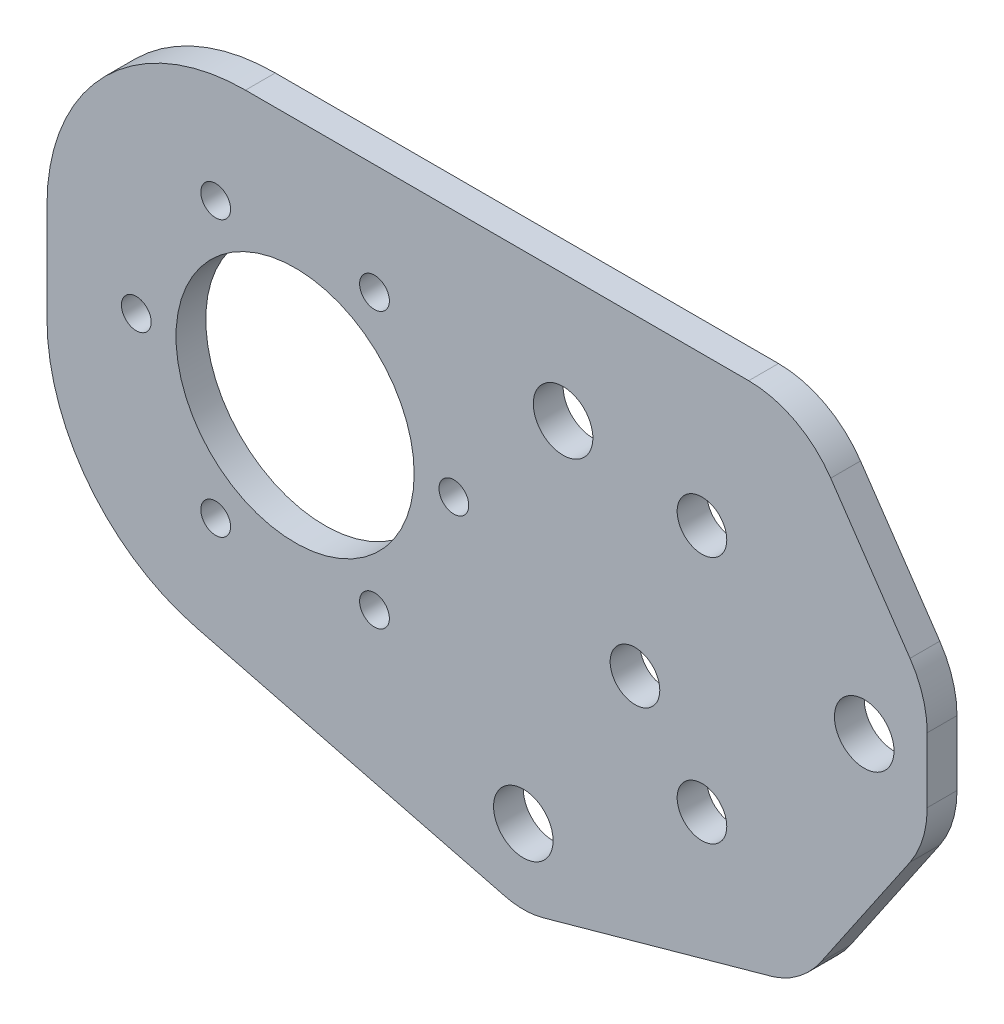
SolidWorks part; units mm, degrees
material "Gerais  - 6061-T6"
ref_plane "Plano frontal" through (0, 0, 0) normal (0, 0, 1) x (1, 0, 0)
ref_plane "Plano superior" through (0, 0, 0) normal (0, 1, 0) x (1, 0, 0)
ref_plane "Plano direito" through (0, 0, 0) normal (1, 0, 0) x (0, 0, -1)
sketch "Esboço1" plane through (0, 0, 0) normal (0, 0, 1) x (1, 0, 0)
  line L0 (56, 50) -> (56, 0) construction
  line L1 (0, 0) -> (76, 0)
  line L2 (0, 0) -> (0, 50)
  line L3 (0, 50) -> (76, 50)
  line L4 (76, 0) -> (76, 50)
  line L5 (66, 50) -> (66, 18.5) construction
  line L6 (65.25, 50) -> (65.25, 18.5) construction
  line L7 (59.25, 12.5) -> (25, 12.5) construction
  circle A0 centre (25, 25) radius 16 construction
  circle A1 centre (59.25, 18.5) radius 9.75 construction
  circle A2 centre (59.25, 18.5) radius 6 construction
  circle A3 centre (25, 25) radius 12.5 construction
  circle A4 centre (59.25, 18.5) radius 2.5
  circle A5 centre (25, 25) radius 12
  circle A6 centre (17, 38.8564) radius 1.5
  circle A7 centre (33, 38.8564) radius 1.5
  circle A8 centre (41, 25) radius 1.5
  circle A9 centre (33, 11.1436) radius 1.5
  circle A10 centre (17, 11.1436) radius 1.5
  circle A11 centre (9, 25) radius 1.5
  point P7 (41, 25)
  point P36 (25, 25)
  dimension "D1" = 32
  dimension "D5" = 12
  dimension "D6" = 19.5
  dimension "D9" = 25
  dimension "D10" = 5
  dimension "D13" = 24
  dimension "D14" = 3
  dimension "D2" = 25
  dimension "D3" = 35
  dimension "D4" = 20
  dimension "D7" = 0.75
  dimension "D8" = 10
  dimension "D11" = 25
  dimension "D12" = 50
  dimension "D15" = 6
extrude "Ressalto-extrusão1" add sketch "Esboço1" along normal blind 3
sketch "Esboço2" plane through (0, 0, 3) normal (0, 0, 1) x (1, 0, 0)
  line L0 (66, 50) -> (66, 0) construction
  line L1 (76, 50) -> (0, 50) construction
  line L2 (0, 0) -> (76, 0) construction
  line L3 (76, 0) -> (76, 50) construction
  circle A0 centre (66, 35) radius 2.5
  circle A1 centre (66, 15) radius 2.5
  dimension "D2" = 5
  dimension "D3" = 5
  dimension "D1" = 10
  dimension "D4" = 15
  dimension "D5" = 15
extrude "Corte-extrusão1" cut sketch "Esboço2" against normal blind 3
fillet "Filete1" radius 20 2 edges at (0, 0, 1.5) (0, 50, 1.5)
sketch "Esboço3" plane through (0, 0, 3) normal (0, 0, 1) x (1, 0, 0)
  circle A0 centre (66, 15) radius 2.5 construction
  circle A1 centre (66, 35) radius 2.5 construction
  circle A2 centre (66, 15) radius 2.5
  circle A3 centre (66, 35) radius 2.5
extrude "Ressalto-extrusão2" add sketch "Esboço3" against normal through all
sketch "Esboço4" plane through (0, 0, 0) normal (0, 0, -1) x (-1, 0, 0)
  line L0 (-20, 0) -> (-76, 0) construction
  line L1 (-20, 0) -> (-76, 0)
  line L5 (-78.9768, 45.6286) -> (-86.9656, 33.897)
  line L6 (-73.1059, -0.8046) -> (-50.0089, -7.2259)
  line L7 (-46.1556, -7.2697) -> (-15.0816, 0.6142)
  line L8 (0, 20) -> (0, 30)
  line L9 (-20, 50) -> (-70.7112, 50)
  line L11 (-73.1059, -0.8046) -> (-50.0089, -7.2259)
  line L12 (-46.1556, -7.2697) -> (-15.0816, 0.6142)
  line L13 (0, 20) -> (0, 30)
  line L14 (-20, 50) -> (-70.7112, 50)
  line L28 (-78.9768, 45.6286) -> (-86.9656, 33.897)
  line L29 (-88.7, 28.2685) -> (-88.7, 21.7315)
  line L30 (-88.7, 28.2685) -> (-88.7, 21.7315)
  line L31 (-86.9656, 16.103) -> (-78.0603, 3.0256)
  line L32 (-86.9656, 16.103) -> (-78.0603, 3.0256)
  line L42 (-76, 0.8122) -> (-76, 0.7319)
  line L43 (-76, 0.8122) -> (-76, 0.7319)
  arc A3 (-50.0089, -7.2259) -> (-46.1556, -7.2697) centre (-48, 0) ccw
  arc A4 (-15.0816, 0.6142) -> (0, 20) centre (-20, 20) ccw
  arc A5 (0, 30) -> (-20, 50) centre (-20, 30) ccw
  arc A6 (-50.0089, -7.2259) -> (-46.1556, -7.2697) centre (-48, 0) ccw
  arc A7 (-15.0816, 0.6142) -> (0, 20) centre (-20, 20) ccw
  arc A8 (0, 30) -> (-20, 50) centre (-20, 30) ccw
  arc A22 (-70.7112, 50) -> (-78.9768, 45.6286) centre (-70.7112, 40) ccw
  arc A23 (-70.7112, 50) -> (-78.9768, 45.6286) centre (-70.7112, 40) ccw
  arc A24 (-86.9656, 33.897) -> (-88.7, 28.2685) centre (-78.7, 28.2685) ccw
  arc A25 (-86.9656, 33.897) -> (-88.7, 28.2685) centre (-78.7, 28.2685) ccw
  arc A26 (-88.7, 21.7315) -> (-86.9656, 16.103) centre (-78.7, 21.7315) ccw
  arc A27 (-88.7, 21.7315) -> (-86.9656, 16.103) centre (-78.7, 21.7315) ccw
  arc A58 (-78.0603, 3.0256) -> (-76, 0.8122) centre (-69.7947, 8.6541) ccw
  arc A59 (-78.0603, 3.0256) -> (-76, 0.8122) centre (-69.7947, 8.6541) ccw
  arc A60 (-76, 0.7319) -> (-73.1059, -0.8046) centre (-70.3513, 7.878) ccw
  arc A61 (-76, 0.7319) -> (-73.1059, -0.8046) centre (-70.3513, 7.878) ccw
  line M13 (-76, 0) -> (-20, 0)
  arc M14 (-20, 0) -> (0, 20) centre (-20, 20) ccw
  dimension "D1" = 0
extrude "Ressalto-extrusão3" add sketch "Esboço4" against normal through all contours L11 A6 L12 M14 M13 region at (47.1179, -2.5799, 0)
sketch "Esboço5" plane through (0, 0, 0) normal (0, 0, -1) x (-1, 0, 0)
  circle A0 centre (-48, 0) radius 3 construction
  circle A1 centre (-48, 43.65) radius 3 construction
  circle A2 centre (-48, 0) radius 3
  circle A3 centre (-48, 43.65) radius 3 construction
  circle A4 centre (-52.0071, 37.1424) radius 3
  circle A5 centre (-25, 25) radius 29.6112 construction
  circle A6 centre (-59.25, 18.5) radius 11 construction
  point P12 (0, 0)
  dimension "D1" = 22
  dimension "D2" = 20
extrude "Corte-extrusão2" cut sketch "Esboço5" against normal through all
sketch "Esboço6" plane through (0, 0, 3) normal (0, 0, 1) x (1, 0, 0)
  line L0 (76, 50) -> (88.7, 31.35)
  line L1 (88.7, 31.35) -> (88.7, 18.65)
  line L2 (88.7, 18.65) -> (76, 0)
  line L3 (76, 0) -> (76, 50) construction
  line L4 (25, 25) -> (88.7, 25) construction
  circle A0 centre (82.35, 25) radius 3
  line M6 (76, 0) -> (76, 50)
  dimension "D2" = 6
  dimension "D3" = 12.7
  dimension "D4" = 6.35
extrude "Ressalto-extrusão4" add sketch "Esboço6" against normal through all contours L4 A0 L1 L0 M6 | L4 L2 L1 A0 M6 region at (80.9945, 34.3345, 3) region at (80.9945, 15.6655, 3)
fillet "Filete2" radius 10 4 edges at (88.7, 18.65, 1.5) (88.7, 31.35, 1.5) (76, 50, 1.5) (76, 0, 1.5)
sketch "Esboço7" plane through (0, 0, 3) normal (0, 0, 1) x (1, 0, 0)
  circle A0 centre (66, 35) radius 2.5
  circle A1 centre (66, 10) radius 2.5
  circle A2 centre (25, 25) radius 12 construction
  dimension "D1" = 5
  dimension "D2" = 25
  dimension "D3" = 41
  dimension "D4" = 15
extrude "Corte-extrusão3" cut sketch "Esboço7" against normal blind 10
